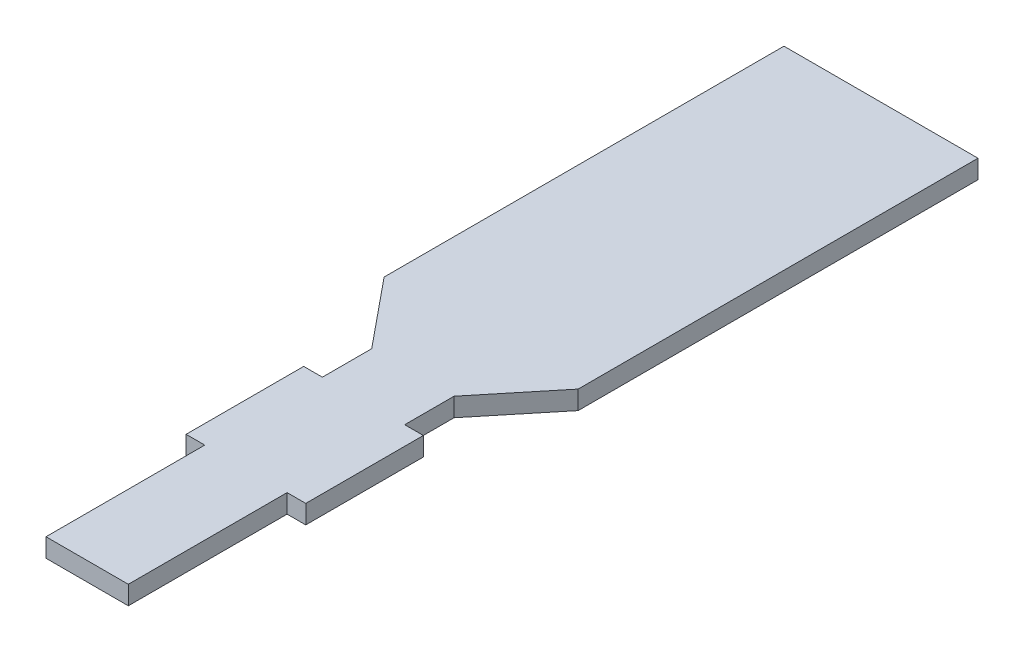
SolidWorks part; units mm, degrees
ref_plane "Front Plane" through (0, 0, 0) normal (0, 0, 1) x (1, 0, 0)
ref_plane "Top Plane" through (0, 0, 0) normal (0, 1, 0) x (1, 0, 0)
ref_plane "Right Plane" through (0, 0, 0) normal (1, 0, 0) x (0, 0, -1)
sketch "Sketch1" plane through (0, 0, 0) normal (0, 1, 0) x (1, 0, 0)
  line L0 (-16.5, 0) -> (16.5, 0)
  line L1 (16.5, 0) -> (16.5, -68)
  line L2 (16.5, -68) -> (7, -79.6082)
  line L3 (7, -79.6082) -> (7, -88)
  line L4 (7, -88) -> (10.175, -88)
  line L5 (10.175, -88) -> (10.175, -108)
  line L6 (10.175, -108) -> (7, -108)
  line L7 (7, -108) -> (7, -135)
  line L8 (7, -135) -> (-7, -135)
  line L9 (0, 0) -> (0, -135) construction
  line L10 (-7, -108) -> (-7, -135)
  line L11 (-10.175, -108) -> (-7, -108)
  line L12 (-10.175, -88) -> (-10.175, -108)
  line L13 (-7, -88) -> (-10.175, -88)
  line L14 (-7, -79.6082) -> (-7, -88)
  line L15 (-16.5, -68) -> (-7, -79.6082)
  line L16 (-16.5, 0) -> (-16.5, -68)
  dimension "D1" = 68
  dimension "D2" = 3.175
  dimension "D3" = 20
  dimension "D4" = 20
  dimension "D5" = 27
  dimension "D6" = 16.5
  dimension "D7" = 7
  dimension "D8" = 15
extrude "Boss-Extrude1" add sketch "Sketch1" along normal blind 3.175
